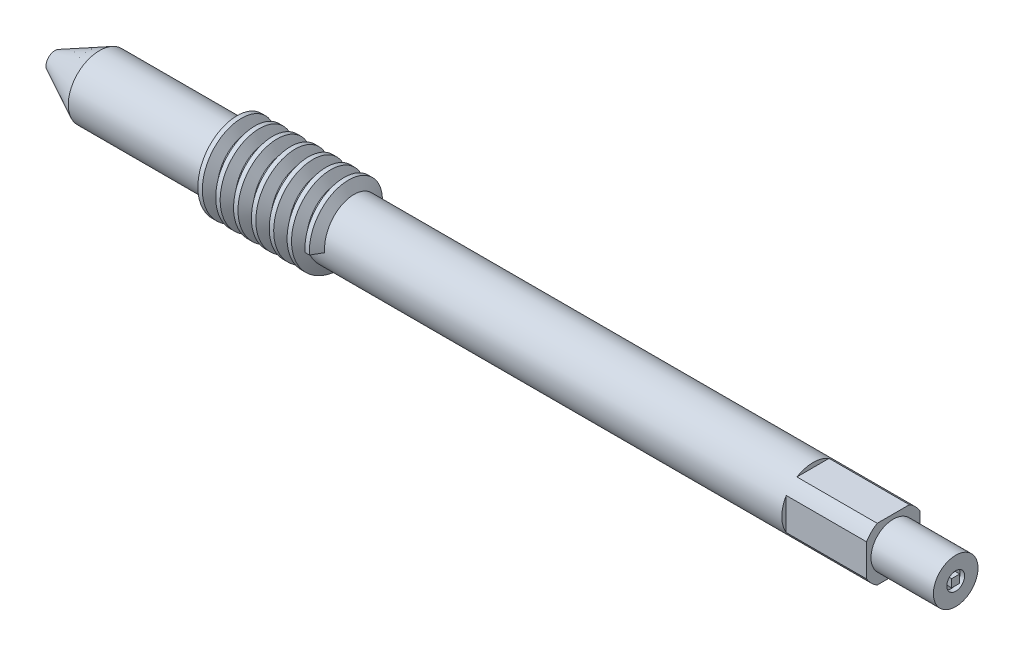
SolidWorks part; units mm, degrees
ref_plane "Спереди" through (0, 0, 0) normal (0, 0, 1) x (1, 0, 0)
ref_plane "Сверху" through (0, 0, 0) normal (0, 1, 0) x (1, 0, 0)
ref_plane "Справа" through (0, 0, 0) normal (1, 0, 0) x (0, 0, -1)
sketch "Эскиз2" plane through (0, 0, 0) normal (0, 0, 1) x (1, 0, 0)
  line L0 (0, 0) -> (0, 1)
  line L1 (0, 1) -> (5, 3.5)
  line L2 (5, 3.5) -> (85, 3.5)
  line L3 (0, 0) -> (53.0431, 0) construction
  line L4 (0, 0) -> (85, 0)
  line L5 (85, 0) -> (85, 3.5)
  dimension "D1" = 1
  dimension "D2" = 5
  dimension "D3" = 3.5
  dimension "D4" = 80
revolve "Повернуть1" add sketch "Эскиз2" angle 360 about L3
sketch "Эскиз3" plane through (85, 0, 0) normal (1, 0, 0) x (0, 0, -1)
  line L0 (1000, 0) -> (-3, 0) construction
  line L1 (-1.8028, -3) -> (1.8028, -3)
  line L2 (-3, -1.8028) -> (-3, 1.8028)
  line L3 (-1.8028, 3) -> (1.8028, 3)
  line L4 (3, -1.8028) -> (3, 1.8028)
  line L5 (-2.4749, -2.4749) -> (2.4749, 2.4749) construction
  line L6 (-2.4749, 2.4749) -> (2.4749, -2.4749) construction
  line L7 (-3.5, 0) -> (-1005.2971, 0) construction
  arc A0 (-1.8028, 3) -> (-3, 1.8028) centre (0, 0) ccw
  arc A1 (3, 1.8028) -> (1.8028, 3) centre (0, 0) ccw
  arc A2 (1.8028, -3) -> (3, -1.8028) centre (0, 0) ccw
  arc A3 (-3, -1.8028) -> (-1.8028, -3) centre (0, 0) ccw
  point P0 (0, 0)
  point P8 (-3, 1.8028)
  point P9 (-3, -1.8028)
  point P10 (3, 1.8028)
  point P11 (3, -1.8028)
  point P12 (1.8028, 3)
  point P13 (-1.8028, 3)
  point P14 (1.8028, -3)
  point P15 (-1.8028, -3)
  dimension "D3" = 7
  dimension "D1" = 6
  dimension "D2" = 6
  dimension "D4" = 3
extrude "Бобышка-Вытянуть1" add sketch "Эскиз3" along normal blind 9
sketch "Эскиз4" plane through (94, 0, 0) normal (1, 0, 0) x (0, 0, -1)
  circle A0 centre (0, 0) radius 2.5
  dimension "D1" = 5
extrude "Бобышка-Вытянуть2" add sketch "Эскиз4" along normal blind 7 contours A0
cosmetic thread "Условное изображение резьбы1" parameters "D1"=5.5, "D2"=3.22
sketch "Эскиз5" plane through (101, 0, 0) normal (1, 0, 0) x (0, 0, -1)
  circle A0 centre (0, 0) radius 1
  dimension "D1" = 2
extrude "Вырез-Вытянуть1" cut sketch "Эскиз5" against normal blind 0.5
sketch "Эскиз6" plane through (100.5, 0, 0) normal (1, 0, 0) x (0, 0, -1)
  line L1 (-0.45, -0.45) -> (0.45, -0.45)
  line L2 (-0.45, -0.45) -> (-0.45, 0.45)
  line L3 (-0.45, 0.45) -> (0.45, 0.45)
  line L4 (0.45, -0.45) -> (0.45, 0.45)
  line L5 (-0.45, -0.45) -> (0.45, 0.45) construction
  line L6 (-0.45, 0.45) -> (0.45, -0.45) construction
  point P0 (0, 0)
  dimension "D1" = 0.9
extrude "Бобышка-Вытянуть3" add sketch "Эскиз6" along normal blind 0.5
thread "Резьба1" pitch 2 method extrude profile "Профиль резьбы1" start angle 0, offset 14, length 13, pitch 2, diameter 7
ref_plane "Плоскость4" through (19, 0, -3.5) normal (0, 1, 0) x (0, 0, 1)
sketch "Профиль резьбы1" plane through (19, 0, -3.5) normal (0, 1, 0) x (0, 0, 1)
  line L0 (0, 0) -> (0, 2) construction
  line L11 (0, 0) -> (0, 1.75)
  line L12 (0, 1.75) -> (-1.0825, 1.125)
  line L13 (-1.0825, 1.125) -> (-1.0825, 0.625)
  line L15 (-1.0825, 0.625) -> (0, 0)
  line L17 (-1.0825, 0.875) -> (0, 0.875) construction
  point P2 (0, 0)
  dimension "Pitch" = 2
  dimension "Profile_Angle" = 60
  dimension "Profile_Land" = 0.5
  dimension "Profile_Height" = 1.0825
